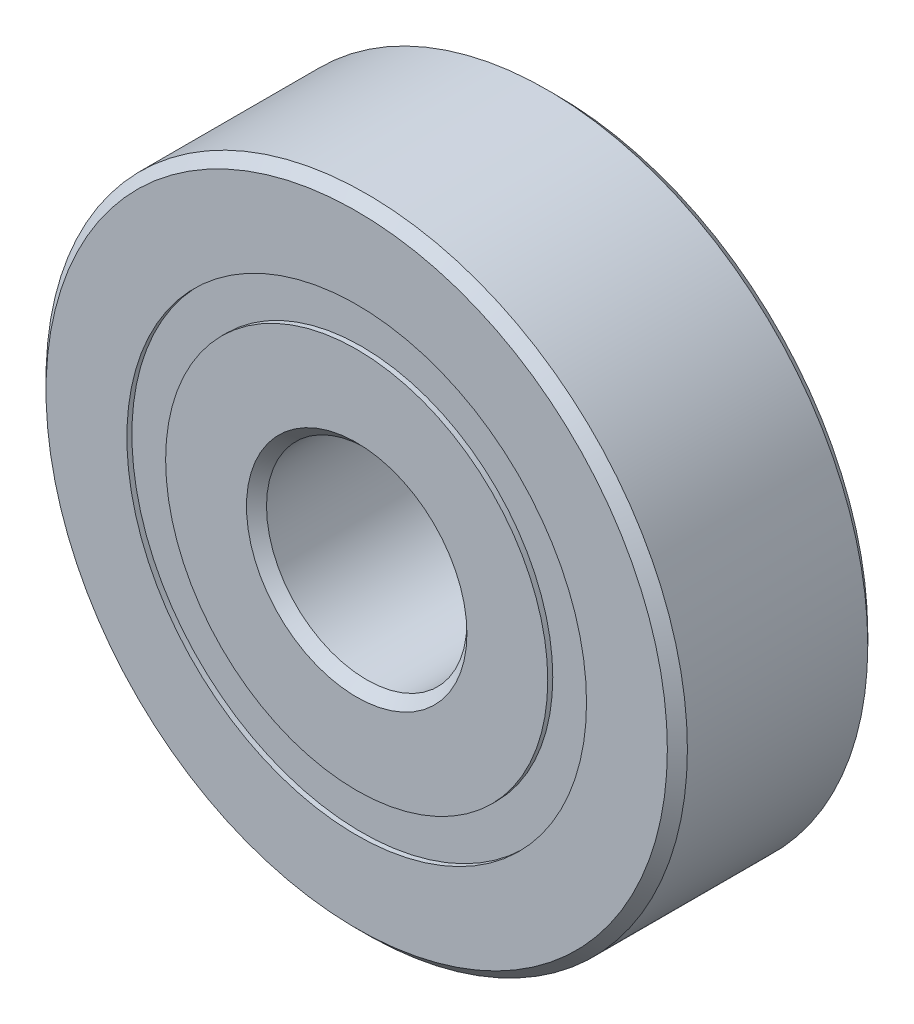
SolidWorks part; units mm, degrees
ref_plane "Front Plane" through (0, 0, 0) normal (0, 0, 1) x (1, 0, 0)
ref_plane "Top Plane" through (0, 0, 0) normal (0, 1, 0) x (1, 0, 0)
ref_plane "Right Plane" through (0, 0, 0) normal (1, 0, 0) x (0, 0, -1)
sketch "Sketch1" plane through (0, 0, 0) normal (1, 0, 0) x (0, 0, -1)
  line L0 (-2.5, 0) -> (2.5, 0) construction
  line L1 (0, 8) -> (0, -8) construction
  line L2 (2.25, 8) -> (-2.25, 8)
  line L3 (-2.25, 8) -> (-2.5, 7.75)
  line L4 (-2.5, 7.75) -> (-2.5, 5.7335)
  line L5 (-2.5, 5.7335) -> (-1.1111, 5.7335)
  line L6 (2.5, 5.7335) -> (1.1111, 5.7335)
  line L7 (2.5, 7.75) -> (2.5, 5.7335)
  line L8 (2.25, 8) -> (2.5, 7.75)
  line L9 (0, 8) -> (0, 5.25) construction
  line L10 (0, 5.25) -> (0, 2.5) construction
  arc A0 (-1.1111, 5.7335) -> (1.1111, 5.7335) centre (0, 5.25) cw
  point P14 (0, 2.5)
  dimension "Width" = 5
  dimension "OD" = 16
  dimension "D1" = 45
  dimension "D2" = 0.25
  dimension "Shaft Dia" = 5
  dimension "D3" = 2.2222
  dimension "D4" = 0.4835
revolve "Revolve1" add sketch "Sketch1" angle 360 about L0
sketch "Sketch3" plane through (0, 0, 0) normal (1, 0, 0) x (0, 0, -1)
  line L0 (-2.5, 4.7665) -> (-1.1111, 4.7665)
  line L1 (0, 8) -> (0, -8) construction
  line L2 (-2.5, 7.75) -> (-2.5, 5.7335) construction
  line L3 (-2.5, 4.7665) -> (-2.5, 2.75)
  line L4 (-2.25, 8) -> (-2.5, 7.75) construction
  line L5 (-2.5, 2.75) -> (-2.25, 2.5)
  line L6 (-2.25, 2.5) -> (2.25, 2.5)
  line L7 (2.25, 8) -> (2.25, -8) construction
  line L8 (2.25, 2.5) -> (2.5, 2.75)
  line L9 (2.5, -7.75) -> (2.5, 7.75) construction
  line L10 (2.5, 2.75) -> (2.5, 4.7665)
  line L11 (2.5, 4.7665) -> (1.1111, 4.7665)
  line L13 (2.25, 8) -> (2.5, 7.75) construction
  arc A0 (1.1111, 5.7335) -> (-1.1111, 5.7335) centre (0, 5.25) ccw construction
  arc A1 (1.1111, 4.7665) -> (-1.1111, 4.7665) centre (0, 5.25) cw
revolve "Revolve3" add sketch "Sketch3" angle 360 about L0
sketch "Sketch4" plane through (0, 0, 0) normal (1, 0, 0) x (0, 0, -1)
  line L0 (-1.2118, 5.25) -> (1.2118, 5.25)
  arc A2 (-1.2118, 5.25) -> (1.2118, 5.25) centre (0, 5.25) cw
  arc A3 (1.1111, 5.7335) -> (-1.1111, 5.7335) centre (0, 5.25) ccw construction
revolve "Revolve4" add sketch "Sketch4" angle 360 about L0
ref_axis "Axis1" through (0, 0, -2.5) along (0, 0, 1)
pattern_circular "CirPattern1" count 12 every 30 about axis through (0, 0, -2.5) along (0, 0, 1) of bodies 104
sketch "Sketch5" plane through (0, 0, 0) normal (1, 0, 0) x (0, 0, -1)
  line L0 (-2.5, 5.7335) -> (-1.1111, 5.7335) construction
  line L1 (-2.375, 5.7335) -> (-1.2118, 5.7335)
  line L2 (-2.375, 5.7335) -> (-2.375, 4.7665)
  line L3 (-2.375, 4.7665) -> (-1.2118, 4.7665)
  line L4 (-1.2118, 5.7335) -> (-1.2118, 4.7665)
  line L5 (-2.5, 4.7665) -> (-1.1111, 4.7665) construction
  line L6 (2.5, 5.7335) -> (1.1111, 5.7335) construction
  line L7 (2.375, 5.7335) -> (1.2118, 5.7335)
  line L8 (2.375, 5.7335) -> (2.375, 4.7665)
  line L9 (2.375, 4.7665) -> (1.2118, 4.7665)
  line L10 (1.2118, 5.7335) -> (1.2118, 4.7665)
  line L11 (2.5, 4.7665) -> (1.1111, 4.7665) construction
  line L12 (-2.25, 8) -> (-2.5, 7.75) construction
  point P18 (-2.375, 7.875)
revolve "Revolve5" add sketch "Sketch5" angle 360 about L0
sketch "Sketch6" plane through (0, 0, 0) normal (1, 0, 0) x (0, 0, -1)
  line L0 (2.5, 0) -> (-2.5, 0) construction
  line L1 (2.5, 5.7335) -> (1.4, 5.7335)
  line L2 (2.5, 5.7335) -> (2.5, 9.5)
  line L3 (2.5, 9.5) -> (1.4, 9.5)
  line L4 (1.4, 5.7335) -> (1.4, 9.5)
  dimension "Th" = 1.1
  dimension "Flange OD" = 19
revolve "Revolve6" [suppressed] add sketch "Sketch6" angle 360 about L0
equation "\"D2@Sketch1\" = \"Width@Sketch1\"*.05"
equation "\"D3@Sketch1\" = \"Width@Sketch1\"/2.25"
equation "\"D4@Sketch1\" = (((\"OD@Sketch1\"-\"Width@Sketch1\")/2)/3.25)/3.5"
equation "\"D2@CirPattern1\" = 360/\"Balls@CirPattern1\""
